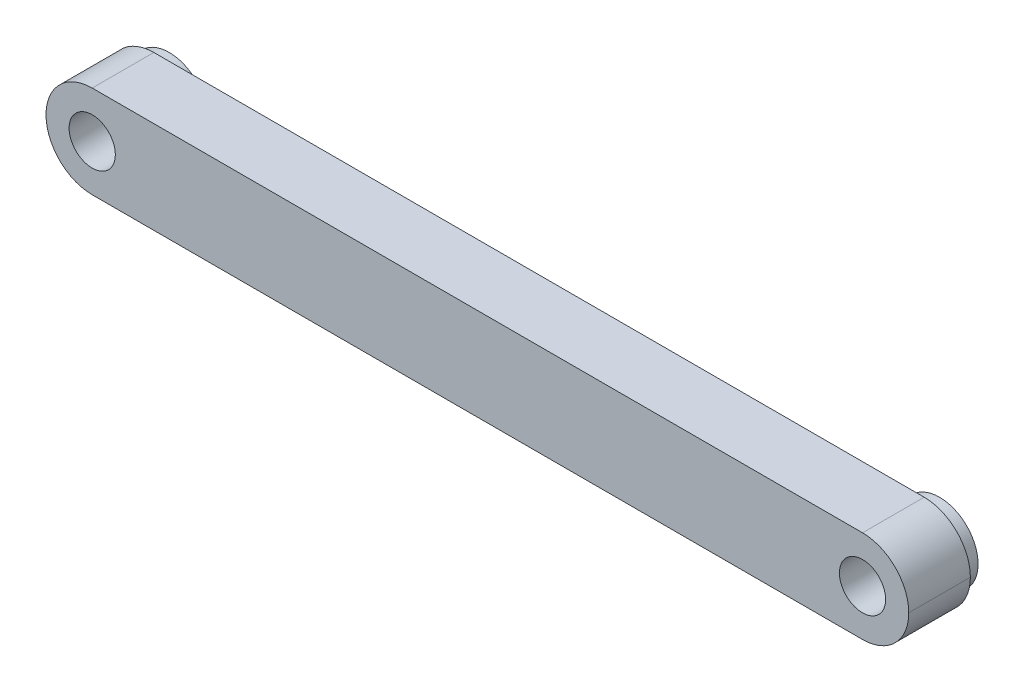
SolidWorks part; units mm, degrees
ref_plane "前视基准面" through (0, 0, 0) normal (0, 0, 1) x (1, 0, 0)
ref_plane "上视基准面" through (0, 0, 0) normal (0, 1, 0) x (1, 0, 0)
ref_plane "右视基准面" through (0, 0, 0) normal (1, 0, 0) x (0, 0, -1)
sketch "草图1" plane through (0, 0, 0) normal (0, 0, 1) x (1, 0, 0)
  line L1 (-28, -3) -> (28, -3)
  line L2 (-28, -3) -> (-28, 3)
  line L3 (-28, 3) -> (28, 3)
  line L4 (28, -3) -> (28, 3)
  line L5 (-28, -3) -> (28, 3) construction
  line L6 (-28, 3) -> (28, -3) construction
  circle A0 centre (-25, 0) radius 1.5
  circle A1 centre (25, 0) radius 1.5
  point P0 (0, 0)
extrude "凸台-拉伸1" add sketch "草图1" along normal blind 4
fillet "圆角1" radius 3 4 edges at (28, -3, 2) (28, 3, 2) (-28, -3, 2) (-28, 3, 2)
sketch "草图2" plane through (0, 0, 0) normal (0, 0, -1) x (-1, 0, 0)
  circle A0 centre (25, 0) radius 1.5
  circle A1 centre (25, 0) radius 2.5
  circle A2 centre (-25, 0) radius 1.5
  circle A3 centre (-25, 0) radius 2.5
extrude "凸台-拉伸2" add sketch "草图2" along normal blind 1
